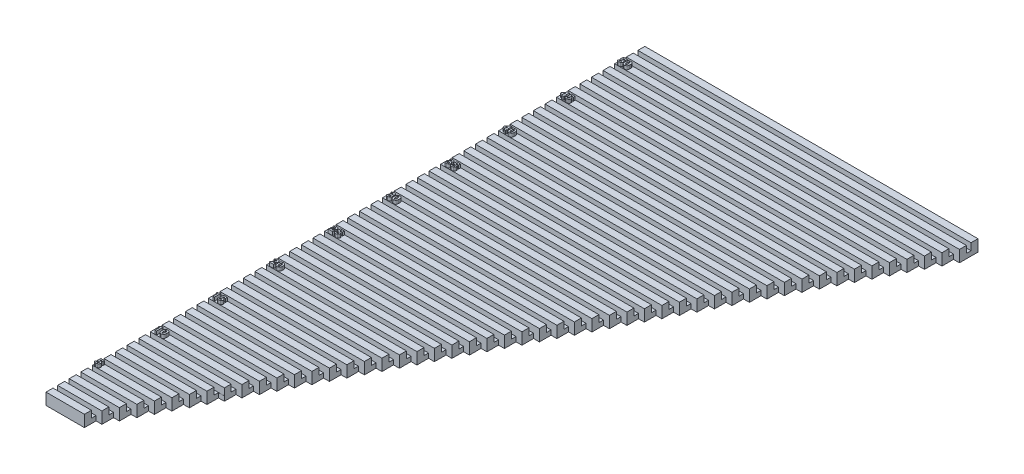
SolidWorks part; units mm, degrees
ref_plane "Alzado" through (0, 0, 0) normal (0, 0, 1) x (1, 0, 0)
ref_plane "Planta" through (0, 0, 0) normal (0, 1, 0) x (1, 0, 0)
ref_plane "Vista lateral" through (0, 0, 0) normal (1, 0, 0) x (0, 0, -1)
sketch "Croquis1" plane through (0, 0, 0) normal (0, 1, 0) x (1, 0, 0)
  line L0 (0, 0) -> (0, 125) construction
  line L1 (70.5, 119) -> (-70.5113, 119)
  line L2 (-70.5113, 125) -> (-70.5113, -125)
  line L4 (-53.96, -125) -> (-53.96, -124) construction
  line L5 (-53.96, -124) -> (-51.42, -124) construction
  line L6 (-51.42, -124) -> (-51.42, -121) construction
  line L7 (-51.42, -121) -> (-51.42, -119) construction
  line L8 (-51.42, -119) -> (-48.88, -119) construction
  line L9 (-48.88, -119) -> (-48.88, -116) construction
  line L10 (-48.88, -116) -> (-48.88, -114) construction
  line L11 (-48.88, -114) -> (-46.34, -114) construction
  line L12 (-46.34, -114) -> (-46.34, -111) construction
  line L13 (-46.34, -111) -> (-46.34, -109)
  line L14 (-46.34, -109) -> (-43.8, -109)
  line L15 (-43.8, -109) -> (-43.8, -106)
  line L16 (-43.8, -106) -> (-43.8, -104)
  line L17 (-43.8, -104) -> (-41.26, -104)
  line L18 (-41.26, -104) -> (-41.26, -101)
  line L19 (-41.26, -101) -> (-41.26, -99)
  line L20 (-41.26, -99) -> (-38.72, -99)
  line L21 (-38.72, -99) -> (-38.72, -96)
  line L22 (-38.72, -96) -> (-38.72, -94)
  line L23 (-38.72, -94) -> (-36.18, -94)
  line L24 (-36.18, -94) -> (-36.18, -91)
  line L25 (-36.18, -91) -> (-36.18, -89)
  line L26 (-36.18, -89) -> (-33.64, -89)
  line L27 (-33.64, -89) -> (-33.64, -86.1155)
  line L28 (-33.64, -86.1155) -> (-33.64, -84)
  line L29 (-33.64, -84) -> (-31.1, -84)
  line L30 (-31.1, -84) -> (-31.1, -81)
  line L31 (-31.1, -81) -> (-31.1, -79)
  line L32 (-31.1, -79) -> (-28.56, -79)
  line L33 (-28.56, -79) -> (-28.56, -76)
  line L34 (-28.56, -76) -> (-28.56, -74)
  line L35 (-28.56, -74) -> (-26.02, -74)
  line L36 (-26.02, -74) -> (-26.02, -71)
  line L37 (-26.02, -71) -> (-26.02, -69)
  line L38 (-26.02, -69) -> (-23.48, -69)
  line L39 (-23.48, -69) -> (-23.48, -66)
  line L40 (-23.48, -66) -> (-23.48, -64)
  line L41 (-23.48, -64) -> (-20.94, -64)
  line L42 (-20.94, -64) -> (-20.94, -61)
  line L43 (-20.94, -61) -> (-20.94, -59)
  line L44 (-20.94, -59) -> (-18.4, -59)
  line L45 (-18.4, -59) -> (-18.4, -56)
  line L46 (-18.4, -56) -> (-18.4, -54)
  line L47 (-18.4, -54) -> (-15.86, -54)
  line L48 (-15.86, -54) -> (-15.86, -51)
  line L49 (-15.86, -51) -> (-15.86, -49)
  line L50 (-15.86, -49) -> (-13.32, -49)
  line L51 (-13.32, -49) -> (-13.32, -46)
  line L52 (-13.32, -46) -> (-13.32, -44)
  line L53 (-13.32, -44) -> (-10.78, -44)
  line L54 (-10.78, -44) -> (-10.78, -41)
  line L55 (-10.78, -41) -> (-10.78, -39)
  line L56 (-10.78, -39) -> (-8.24, -39)
  line L57 (-8.24, -39) -> (-8.24, -36)
  line L58 (-8.24, -36) -> (-8.24, -34)
  line L59 (-8.24, -34) -> (-5.7, -34)
  line L60 (-5.7, -34) -> (-5.7, -31)
  line L61 (-5.7, -31) -> (-5.7, -29)
  line L62 (-5.7, -29) -> (-3.16, -29)
  line L63 (-3.16, -29) -> (-3.16, -26)
  line L64 (-3.16, -26) -> (-3.16, -24)
  line L65 (-3.16, -24) -> (-0.62, -24)
  line L66 (-0.62, -24) -> (-0.62, -21)
  line L67 (-0.62, -21) -> (-0.62, -19)
  line L68 (-0.62, -19) -> (1.92, -19)
  line L69 (1.92, -19) -> (1.92, -16)
  line L70 (1.92, -16) -> (1.92, -14)
  line L71 (1.92, -14) -> (4.46, -14)
  line L72 (4.46, -14) -> (4.46, -11)
  line L73 (4.46, -11) -> (4.46, -9)
  line L74 (4.46, -9) -> (7, -9)
  line L75 (7, -9) -> (7, -6)
  line L76 (7, -6) -> (7, -4)
  line L77 (7, -4) -> (9.54, -4)
  line L78 (9.54, -4) -> (9.54, -1)
  line L79 (9.54, -1) -> (9.54, 1)
  line L80 (9.54, 1) -> (12.08, 1)
  line L81 (12.08, 1) -> (12.08, 4)
  line L82 (12.08, 4) -> (12.08, 6)
  line L83 (12.08, 6) -> (14.62, 6)
  line L84 (14.62, 6) -> (14.62, 9)
  line L85 (14.62, 9) -> (14.62, 11)
  line L86 (14.62, 11) -> (17.16, 11)
  line L87 (17.16, 11) -> (17.16, 14)
  line L88 (17.16, 14) -> (17.16, 16)
  line L89 (17.16, 16) -> (19.7, 16)
  line L90 (19.7, 16) -> (19.7, 19)
  line L91 (19.7, 19) -> (19.7, 21)
  line L92 (19.7, 21) -> (22.24, 21)
  line L93 (22.24, 21) -> (22.24, 24)
  line L94 (22.24, 24) -> (22.24, 26)
  line L95 (22.24, 26) -> (24.78, 26)
  line L96 (24.78, 26) -> (24.78, 29)
  line L97 (24.78, 29) -> (24.78, 31)
  line L98 (24.78, 31) -> (27.32, 31)
  line L99 (27.32, 31) -> (27.32, 34)
  line L100 (27.32, 34) -> (27.32, 36)
  line L101 (27.32, 36) -> (29.86, 36)
  line L102 (29.86, 36) -> (29.86, 39)
  line L103 (29.86, 39) -> (29.86, 41)
  line L104 (29.86, 41) -> (32.4, 41)
  line L105 (32.4, 41) -> (32.4, 44)
  line L106 (32.4, 44) -> (32.4, 46)
  line L107 (32.4, 46) -> (34.94, 46)
  line L108 (34.94, 46) -> (34.94, 49)
  line L109 (34.94, 49) -> (34.94, 51)
  line L110 (34.94, 51) -> (37.48, 51)
  line L111 (37.48, 51) -> (37.48, 54)
  line L112 (37.48, 54) -> (37.48, 56)
  line L113 (37.48, 56) -> (40.02, 56)
  line L114 (40.02, 56) -> (40.02, 59)
  line L115 (40.02, 59) -> (40.02, 61)
  line L116 (40.02, 61) -> (42.56, 61)
  line L117 (42.56, 61) -> (42.56, 64)
  line L118 (42.56, 64) -> (42.56, 66)
  line L119 (42.56, 66) -> (45.1, 66)
  line L120 (45.1, 66) -> (45.1, 69)
  line L121 (45.1, 69) -> (45.1, 71)
  line L122 (45.1, 71) -> (47.64, 71)
  line L123 (47.64, 71) -> (47.64, 74)
  line L124 (47.64, 74) -> (47.64, 76)
  line L125 (47.64, 76) -> (50.18, 76)
  line L126 (50.18, 76) -> (50.18, 79)
  line L127 (50.18, 79) -> (50.18, 81)
  line L128 (50.18, 81) -> (52.72, 81)
  line L129 (52.72, 81) -> (52.72, 84)
  line L130 (52.72, 84) -> (52.72, 86)
  line L131 (52.72, 86) -> (55.26, 86)
  line L132 (55.26, 86) -> (55.26, 89)
  line L133 (55.26, 89) -> (55.26, 91)
  line L134 (55.26, 91) -> (57.8, 91)
  line L135 (57.8, 91) -> (57.8, 94)
  line L136 (57.8, 94) -> (57.8, 96)
  line L137 (57.8, 96) -> (60.34, 96)
  line L138 (60.34, 96) -> (60.34, 99)
  line L139 (60.34, 99) -> (60.34, 101)
  line L140 (60.34, 101) -> (62.88, 101)
  line L141 (62.88, 101) -> (62.88, 104)
  line L142 (62.88, 104) -> (62.88, 106)
  line L143 (62.88, 106) -> (65.42, 106)
  line L144 (65.42, 106) -> (65.42, 109)
  line L145 (65.42, 109) -> (65.42, 111)
  line L146 (65.42, 111) -> (67.96, 111)
  line L147 (67.96, 111) -> (67.96, 114)
  line L148 (67.96, 114) -> (67.96, 116)
  line L149 (67.96, 116) -> (70.5, 116)
  line L150 (70.5, 116) -> (70.5, 119)
  line L151 (70.5, 119) -> (70.5, 121)
  line L152 (70.5, 121) -> (73.04, 121)
  line L153 (73.04, 121) -> (73.04, 124)
  line L154 (73.04, 124) -> (73.04, 126)
  line L155 (73.04, 126) -> (73.04, 129)
  line L156 (73.04, 129) -> (-70.5113, 129)
  line L157 (-70.5113, 129) -> (-70.5113, 125)
  line L158 (-53.96, -125) -> (-53.96, -126)
  line L159 (-53.96, -126) -> (-53.96, -129)
  line L160 (-53.96, -129) -> (-70.5113, -129)
  line L161 (-70.5113, -129) -> (-70.5113, -125)
  line L162 (67.96, 116) -> (-70.5113, 116)
  line L163 (-53.96, -125) -> (-53.96, -124)
  line L164 (-53.96, -124) -> (-51.42, -124)
  line L165 (-51.42, -124) -> (-51.42, -121)
  line L166 (-51.42, -121) -> (-51.42, -119)
  line L167 (-51.42, -119) -> (-48.88, -119)
  line L168 (-48.88, -119) -> (-48.88, -116)
  line L169 (-48.88, -116) -> (-48.88, -114)
  line L170 (-48.88, -114) -> (-46.34, -114)
  line L171 (-46.34, -114) -> (-46.34, -111)
  line L172 (-53.96, -126) -> (-70.5113, -126)
  line L173 (-53.96, -124) -> (-70.5113, -124)
  line L174 (-51.42, -121) -> (-70.5113, -121)
  line L175 (-51.42, -119) -> (-70.5113, -119)
  line L176 (-48.88, -116) -> (-70.5113, -116)
  line L177 (-48.88, -114) -> (-70.5113, -114)
  line L178 (-46.34, -109) -> (-70.5113, -109)
  line L179 (-46.34, -111) -> (-70.5113, -111)
  line L180 (-43.8, -106) -> (-70.5113, -106)
  line L181 (-43.8, -104) -> (-70.5113, -104)
  line L182 (-41.26, -101) -> (-70.5113, -101)
  line L183 (-41.26, -99) -> (-70.5113, -99)
  line L184 (-38.72, -96) -> (-70.5113, -96)
  line L185 (-38.72, -94) -> (-70.5113, -94)
  line L186 (-36.18, -91) -> (-70.5113, -91)
  line L187 (-36.18, -89) -> (-70.5113, -89)
  line L188 (70.5, 121) -> (-70.5113, 121)
  line L189 (73.04, 124) -> (-70.5113, 124)
  line L190 (73.04, 126) -> (-70.5113, 126)
  line L191 (67.96, 114) -> (-70.5113, 114)
  line L192 (65.42, 111) -> (-70.5113, 111)
  line L193 (65.42, 109) -> (-70.5113, 109)
  line L194 (62.88, 106) -> (-70.5113, 106)
  line L195 (62.88, 104) -> (-70.5113, 104)
  line L196 (60.34, 101) -> (-70.5113, 101)
  line L197 (60.34, 99) -> (-70.5113, 99)
  line L198 (57.8, 96) -> (-70.5113, 96)
  line L199 (57.8, 94) -> (-70.5113, 94)
  line L200 (55.26, 91) -> (-70.5113, 91)
  line L201 (55.26, 89) -> (-70.5113, 89)
  line L202 (52.72, 86) -> (-70.5113, 86)
  line L203 (52.72, 84) -> (-70.5113, 84)
  line L204 (50.18, 81) -> (-70.5113, 81)
  line L205 (50.18, 79) -> (-70.5113, 79)
  line L206 (47.64, 76) -> (-70.5113, 76)
  line L207 (47.64, 74) -> (-70.5113, 74)
  line L208 (45.1, 71) -> (-70.5113, 71)
  line L209 (45.1, 69) -> (-70.5113, 69)
  line L210 (42.56, 66) -> (-70.5113, 66)
  line L211 (42.56, 64) -> (-70.5113, 64)
  line L212 (40.02, 61) -> (-70.5113, 61)
  line L213 (40.02, 59) -> (-70.5113, 59)
  line L214 (37.48, 56) -> (-70.5113, 56)
  line L215 (37.48, 54) -> (-70.5113, 54)
  line L216 (34.94, 51) -> (-70.5113, 51)
  line L217 (34.94, 49) -> (-70.5113, 49)
  line L218 (32.4, 46) -> (-70.5113, 46)
  line L219 (32.4, 44) -> (-70.5113, 44)
  line L220 (29.86, 41) -> (-70.5113, 41)
  line L221 (29.86, 39) -> (-70.5113, 39)
  line L222 (27.32, 36) -> (-70.5113, 36)
  line L223 (27.32, 35) -> (-70.5113, 35) construction
  line L224 (27.32, 34) -> (-70.5113, 34)
  line L225 (24.78, 31) -> (-70.5113, 31)
  line L226 (24.78, 29) -> (-70.5113, 29)
  line L227 (22.24, 26) -> (-70.5113, 26)
  line L228 (22.24, 24) -> (-70.5113, 24)
  line L229 (19.7, 21) -> (-70.5113, 21)
  line L230 (19.7, 19) -> (-70.5113, 19)
  line L231 (17.16, 16) -> (-70.5113, 16)
  line L232 (17.16, 14) -> (-70.5113, 14)
  line L233 (14.62, 11) -> (-70.5113, 11)
  line L234 (14.62, 9) -> (-70.5113, 9)
  line L235 (12.08, 6) -> (-70.5113, 6)
  line L236 (12.08, 4) -> (-70.5113, 4)
  line L237 (9.54, 1) -> (-70.5113, 1)
  line L238 (9.54, -1) -> (-70.5113, -1)
  line L239 (7, -4) -> (-70.5113, -4)
  line L240 (7, -6) -> (-70.5113, -6)
  line L241 (4.46, -9) -> (-70.5113, -9)
  line L242 (4.46, -11) -> (-70.5113, -11)
  line L243 (1.92, -14) -> (-70.5113, -14)
  line L244 (1.92, -16) -> (-70.5113, -16)
  line L245 (-0.62, -19) -> (-70.5113, -19)
  line L246 (-0.62, -21) -> (-70.5113, -21)
  line L247 (-3.16, -24) -> (-70.5113, -24)
  line L248 (-3.16, -26) -> (-70.5113, -26)
  line L249 (-5.7, -29) -> (-70.5113, -29)
  line L250 (-5.7, -31) -> (-70.5113, -31)
  line L251 (-8.24, -34) -> (-70.5113, -34)
  line L252 (-8.24, -36) -> (-70.5113, -36)
  line L253 (-10.78, -39) -> (-70.5113, -39)
  line L254 (-10.78, -41) -> (-70.5113, -41)
  line L255 (-13.32, -44) -> (-70.5113, -44)
  line L256 (-13.32, -46) -> (-70.5113, -46)
  line L257 (-15.86, -49) -> (-70.5113, -49)
  line L258 (-15.86, -51) -> (-70.5113, -51)
  line L259 (-18.4, -54) -> (-70.5113, -54)
  line L260 (-18.4, -56) -> (-70.5113, -56)
  line L261 (-20.94, -59) -> (-70.5113, -59)
  line L262 (-20.94, -61) -> (-70.5113, -61)
  line L263 (-23.48, -64) -> (-70.5113, -64)
  line L264 (-23.48, -66) -> (-70.5113, -66)
  line L265 (-26.02, -69) -> (-70.5113, -69)
  line L266 (-26.02, -71) -> (-70.5113, -71)
  line L267 (-28.56, -74) -> (-70.5113, -74)
  line L268 (-28.56, -76) -> (-70.5113, -76)
  line L269 (-31.1, -79) -> (-70.5113, -79)
  line L270 (-31.1, -81) -> (-70.5113, -81)
  line L271 (-33.64, -84) -> (-70.5113, -84)
  line L272 (-33.64, -86.1155) -> (-70.5113, -86.1155)
  point P6 (0, 125)
extrude "Saliente-Extruir1" add sketch "Croquis1" along normal blind 5 contours L190 L155 L156 L157 | L153 L189 L2 L188 L152 | L162 L149 L150 L1 L2 | L192 L146 L147 L191 L2 | L194 L143 L144 L193 L2 | L196 L140 L141 L195 L2 | L198 L137 L138 L197 L2 | L200 L134 L135 L199 L2 | L202 L131 L132 L201 L2 | L204 L128 L129 L203 L2 | L206 L125 L126 L205 L2 | L208 L122 L123 L207 L2 | L210 L119 L120 L209 L2 | L212 L116 L117 L211 L2 | L214 L113 L114 L213 L2 | L216 L110 L111 L215 L2 | L218 L107 L108 L217 L2 | L220 L104 L105 L219 L2 | L222 L101 L102 L221 L2 | L225 L98 L99 L224 L2 | L227 L95 L96 L226 L2 | L229 L92 L93 L228 L2 | L231 L89 L90 L230 L2 | L233 L86 L87 L232 L2 | L235 L83 L84 L234 L2 | L237 L80 L81 L236 L2 | L239 L77 L78 L238 L2 | L241 L74 L75 L240 L2 | L243 L71 L72 L242 L2 | L245 L68 L69 L244 L2 | L247 L65 L66 L246 L2 | L249 L62 L63 L248 L2 | L251 L59 L60 L250 L2 | L253 L56 L57 L252 L2 | L255 L53 L54 L254 L2 | L257 L50 L51 L256 L2 | L259 L47 L48 L258 L2 | L261 L44 L45 L260 L2 | L263 L41 L42 L262 L2 | L265 L38 L39 L264 L2 | L267 L35 L36 L266 L2 | L269 L32 L33 L268 L2 | L271 L29 L30 L270 L2 | L27 L272 L2 L187 L26 | L24 L186 L2 L185 L23 | L21 L184 L2 L183 L20 | L18 L182 L2 L181 L17 | L15 L180 L2 L178 L14 | L171 L179 L2 L177 L170 | L168 L176 L2 L175 L167 | L165 L174 L2 L173 L164 | L159 L172 L161 L160 region at (-0.0057, 0, -117.5) region at (1.2643, 0, -122.5) region at (-1.2757, 0, -112.5) region at (1.2643, 0, -127.5) region at (-2.5457, 0, -107.5) region at (-3.8157, 0, -102.5) region at (-5.0857, 0, -97.5) region at (-6.3557, 0, -92.5) region at (-7.6257, 0, -87.5) region at (-8.8957, 0, -82.5) region at (-10.1657, 0, -77.5) region at (-11.4357, 0, -72.5) region at (-12.7057, 0, -67.5) region at (-13.9757, 0, -62.5) region at (-15.2457, 0, -57.5) region at (-16.5157, 0, -52.5) region at (-17.7857, 0, -47.5) region at (-19.0557, 0, -42.5) region at (-20.3257, 0, -37.5) region at (-21.5957, 0, -32.5) region at (-22.8657, 0, -27.5) region at (-24.1357, 0, -22.5) region at (-25.4057, 0, -17.5) region at (-26.6757, 0, -12.5) region at (-27.9457, 0, -7.5) region at (-29.2157, 0, -2.5) region at (-30.4857, 0, 2.5) region at (-31.7557, 0, 7.5) region at (-33.0257, 0, 12.5) region at (-34.2957, 0, 17.5) region at (-35.5657, 0, 22.5) region at (-36.8357, 0, 27.5) region at (-38.1057, 0, 32.5) region at (-39.3757, 0, 37.5) region at (-40.6457, 0, 42.5) region at (-41.9157, 0, 47.5) region at (-43.1857, 0, 52.5) region at (-44.4557, 0, 57.5) region at (-45.7257, 0, 62.5) region at (-46.9957, 0, 67.5) region at (-48.2657, 0, 72.5) region at (-49.5357, 0, 77.5) region at (-50.8057, 0, 82.5) region at (-52.0757, 0, 87.5578) region at (-53.3457, 0, 92.5) region at (-54.6157, 0, 97.5) region at (-55.8857, 0, 102.5) region at (-57.1557, 0, 107.5) region at (-58.4257, 0, 112.5) region at (-59.6957, 0, 117.5) region at (-60.9657, 0, 122.5) region at (-62.2357, 0, 127.5)
sketch "Croquis2" plane through (0, 0, 0) normal (0, -1, 0) x (1, 0, 0)
  line L0 (-70.5113, -129) -> (-70.5113, 129)
  line L1 (-70.5113, 129) -> (-53.96, 129)
  line L2 (-53.96, 129) -> (-53.96, 124)
  line L3 (-51.42, 124) -> (-70.5113, 124) construction
  line L4 (-53.96, 124) -> (-51.42, 124)
  line L5 (-51.42, 124) -> (-51.42, 119)
  line L6 (-48.88, 119) -> (-70.5113, 119) construction
  line L7 (-51.42, 119) -> (-48.88, 119)
  line L8 (-48.88, 119) -> (-48.88, 114)
  line L9 (-46.34, 114) -> (-70.5113, 114) construction
  line L10 (-48.88, 114) -> (-46.34, 114)
  line L11 (-46.34, 114) -> (-46.34, 109)
  line L12 (-43.8, 109) -> (-70.5113, 109) construction
  line L13 (-46.34, 109) -> (-43.8, 109)
  line L14 (-43.8, 109) -> (-43.8, 106) construction
  line L15 (-43.8, 109) -> (-43.8, 104)
  line L16 (-41.26, 104) -> (-70.5113, 104) construction
  line L17 (-43.8, 104) -> (-41.26, 104)
  line L18 (-41.26, 104) -> (-41.26, 99)
  line L19 (-38.72, 99) -> (-70.5113, 99) construction
  line L20 (-41.26, 99) -> (-38.72, 99)
  line L21 (-38.72, 99) -> (-38.72, 94)
  line L22 (-36.18, 94) -> (-70.5113, 94) construction
  line L23 (-38.72, 94) -> (-36.18, 94)
  line L24 (-36.18, 94) -> (-36.18, 89.0623)
  line L25 (-36.18, 89.0623) -> (-33.64, 89)
  line L26 (-33.64, 89) -> (-33.64, 84)
  line L27 (-31.1, 84) -> (-70.5113, 84) construction
  line L28 (-33.64, 84) -> (-31.1, 84)
  line L29 (-31.1, 84) -> (-31.1, 79)
  line L30 (-28.56, 79) -> (-70.5113, 79) construction
  line L31 (-31.1, 79) -> (-28.56, 79)
  line L32 (-28.56, 79) -> (-28.56, 74)
  line L33 (-26.02, 74) -> (-70.5113, 74) construction
  line L34 (-28.56, 74) -> (-26.02, 74)
  line L35 (-26.02, 74) -> (-26.02, 69)
  line L36 (-23.48, 69) -> (-70.5113, 69) construction
  line L37 (-26.02, 69) -> (-23.48, 69)
  line L38 (-23.48, 69) -> (-23.48, 64)
  line L39 (-20.94, 64) -> (-70.5113, 64) construction
  line L40 (-23.48, 64) -> (-20.94, 64)
  line L41 (-20.94, 64) -> (-20.94, 59)
  line L42 (-18.4, 59) -> (-70.5113, 59) construction
  line L43 (-20.94, 59) -> (-18.4, 59)
  line L44 (-18.4, 59) -> (-18.4, 56) construction
  line L45 (-18.4, 59) -> (-18.4, 54)
  line L46 (-15.86, 54) -> (-70.5113, 54) construction
  line L47 (-18.4, 54) -> (-15.86, 54)
  line L48 (-15.86, 54) -> (-15.86, 49)
  line L49 (-13.32, 49) -> (-70.5113, 49) construction
  line L50 (-15.86, 49) -> (-13.32, 49)
  line L51 (-13.32, 49) -> (-13.32, 44)
  line L52 (-10.78, 44) -> (-70.5113, 44) construction
  line L53 (-13.32, 44) -> (-10.78, 44)
  line L54 (-10.78, 44) -> (-10.78, 39)
  line L55 (-8.24, 39) -> (-70.5113, 39) construction
  line L56 (-10.78, 39) -> (-8.24, 39)
  line L57 (-8.24, 39) -> (-8.24, 34)
  line L58 (-5.7, 34) -> (-70.5113, 34) construction
  line L59 (-8.24, 34) -> (-5.7, 34)
  line L60 (-5.7, 34) -> (-5.7, 29)
  line L61 (-3.16, 29) -> (-70.5113, 29) construction
  line L62 (-5.7, 29) -> (-3.16, 29)
  line L63 (-3.16, 29) -> (-3.16, 24)
  line L64 (-0.62, 24) -> (-70.5113, 24) construction
  line L65 (-3.16, 24) -> (-0.62, 24)
  line L66 (-0.62, 24) -> (-0.62, 19)
  line L67 (1.92, 19) -> (-70.5113, 19) construction
  line L68 (-0.62, 19) -> (1.92, 19)
  line L69 (1.92, 19) -> (1.92, 14)
  line L70 (4.46, 14) -> (-70.5113, 14) construction
  line L71 (1.92, 14) -> (4.46, 14)
  line L72 (4.46, 14) -> (4.46, 9)
  line L73 (7, 9) -> (-70.5113, 9) construction
  line L74 (4.46, 9) -> (7, 9)
  line L75 (7, 9) -> (7, 4)
  line L76 (9.54, 4) -> (-70.5113, 4) construction
  line L77 (7, 4) -> (9.54, 4)
  line L78 (9.54, 4) -> (9.54, -1)
  line L79 (12.08, -1) -> (-70.5113, -1) construction
  line L80 (9.54, -1) -> (12.08, -1)
  line L81 (12.08, -1) -> (12.08, -6)
  line L82 (14.62, -6) -> (-70.5113, -6) construction
  line L83 (12.08, -6) -> (14.62, -6)
  line L84 (14.62, -6) -> (14.62, -11)
  line L85 (17.16, -11) -> (-70.5113, -11) construction
  line L86 (14.62, -11) -> (17.16, -11)
  line L87 (17.16, -11) -> (17.16, -16)
  line L88 (19.7, -16) -> (-70.5113, -16) construction
  line L89 (17.16, -16) -> (19.7, -16)
  line L90 (19.7, -16) -> (19.7, -19) construction
  line L91 (19.7, -16) -> (19.7, -21)
  line L92 (22.24, -21) -> (-70.5113, -21) construction
  line L93 (19.7, -21) -> (22.24, -21)
  line L94 (22.24, -21) -> (22.24, -26)
  line L95 (24.78, -26) -> (-70.5113, -26) construction
  line L96 (22.24, -26) -> (24.78, -26)
  line L97 (24.78, -26) -> (24.78, -31)
  line L98 (27.32, -31) -> (-70.5113, -31) construction
  line L99 (24.78, -31) -> (27.32, -31)
  line L100 (27.32, -31) -> (27.32, -36)
  line L101 (29.86, -36) -> (-70.5113, -36) construction
  line L102 (27.32, -36) -> (29.86, -36)
  line L103 (29.86, -36) -> (29.86, -39)
  line L104 (29.86, -39) -> (29.86, -41)
  line L105 (32.4, -41) -> (-70.5113, -41) construction
  line L106 (29.86, -41) -> (32.4, -41)
  line L107 (32.4, -41) -> (32.4, -46)
  line L108 (34.94, -46) -> (-70.5113, -46) construction
  line L109 (32.4, -46) -> (34.94, -46)
  line L110 (34.94, -46) -> (34.94, -51)
  line L111 (37.48, -51) -> (-70.5113, -51) construction
  line L112 (34.94, -51) -> (37.48, -51)
  line L113 (37.48, -51) -> (37.48, -56)
  line L114 (40.02, -56) -> (-70.5113, -56) construction
  line L115 (37.48, -56) -> (40.02, -56)
  line L116 (40.02, -56) -> (40.02, -61)
  line L117 (42.56, -61) -> (-70.5113, -61) construction
  line L118 (40.02, -61) -> (42.56, -61)
  line L119 (42.56, -61) -> (42.56, -66)
  line L120 (45.1, -66) -> (-70.5113, -66) construction
  line L121 (42.56, -66) -> (45.1, -66)
  line L122 (45.1, -66) -> (45.1, -71)
  line L123 (47.64, -71) -> (-70.5113, -71) construction
  line L124 (45.1, -71) -> (47.64, -71)
  line L125 (47.64, -71) -> (47.64, -76)
  line L126 (50.18, -76) -> (-70.5113, -76) construction
  line L127 (47.64, -76) -> (50.18, -76)
  line L128 (50.18, -76) -> (50.18, -81)
  line L129 (52.72, -81) -> (-70.5113, -81) construction
  line L130 (50.18, -81) -> (52.72, -81)
  line L131 (52.72, -81) -> (52.72, -86)
  line L132 (55.26, -86) -> (-70.5113, -86) construction
  line L133 (52.72, -86) -> (55.26, -86)
  line L134 (55.26, -86) -> (55.26, -91)
  line L135 (57.8, -91) -> (-70.5113, -91) construction
  line L136 (55.26, -91) -> (57.8, -91)
  line L137 (57.8, -91) -> (57.8, -96)
  line L138 (60.34, -96) -> (-70.5113, -96) construction
  line L139 (57.8, -96) -> (60.34, -96)
  line L140 (60.34, -96) -> (60.34, -99) construction
  line L141 (60.34, -96) -> (60.34, -101)
  line L142 (62.88, -101) -> (-70.5113, -101) construction
  line L143 (60.34, -101) -> (62.88, -101)
  line L144 (62.88, -101) -> (62.88, -104)
  line L145 (62.88, -104) -> (62.88, -106)
  line L146 (65.42, -106) -> (-70.5113, -106) construction
  line L147 (62.88, -106) -> (65.42, -106)
  line L148 (65.42, -106) -> (65.42, -111)
  line L149 (67.96, -111) -> (-70.5113, -111) construction
  line L150 (65.42, -111) -> (67.96, -111)
  line L151 (67.96, -111) -> (67.96, -116)
  line L152 (70.5, -116) -> (-70.5113, -116) construction
  line L153 (67.96, -116) -> (70.5, -116)
  line L154 (70.5, -116) -> (70.5, -121)
  line L155 (73.04, -121) -> (-70.5113, -121) construction
  line L156 (70.5, -121) -> (73.04, -121)
  line L157 (73.04, -121) -> (73.04, -129)
  line L158 (73.04, -129) -> (-70.5113, -129)
extrude "Saliente-Extruir2" add sketch "Croquis2" against normal blind 2
sketch "Croquis3" plane through (0, 5, 0) normal (0, 1, 0) x (1, 0, 0)
  line L0 (0, 0) -> (-70.5113, 0) construction
  line L1 (-70.5113, -1) -> (-70.5113, 1) construction
  line L2 (-70.5113, 17.5) -> (-70.5113, -7.5) construction
  line L3 (-70.5113, 19) -> (-70.5113, 16) construction
  line L4 (-70.5113, -6) -> (-70.5113, -9) construction
  line L5 (-70.5113, 5) -> (-60.6351, 5) construction
  text T0 "5" font "Commons" height in points 8
  text T1 "10" font "Commons" height in points 8
  text T2 "15" font "Commons" height in points 8
  text T3 "20" font "Commons" height in points 8
  text T4 "25" font "Commons" height in points 8
  text T5 "30" font "Commons" height in points 8
  text T6 "35" font "Commons" height in points 8
  text T7 "40" font "Commons" height in points 8
  text T8 "45" font "Commons" height in points 8
  text T9 "50" font "Commons" height in points 8
extrude "Saliente-Extruir4" add sketch "Croquis3" along normal blind 1.5
